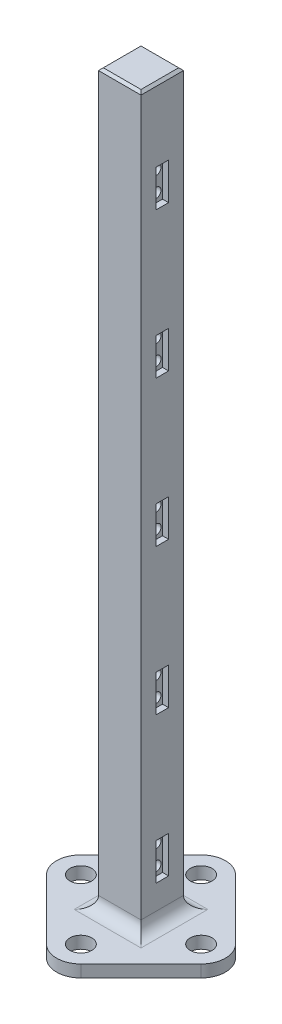
SolidWorks part; units mm, degrees
ref_plane "Front" through (0, 0, 0) normal (0, 0, 1) x (1, 0, 0)
ref_plane "Top" through (0, 0, 0) normal (0, 1, 0) x (1, 0, 0)
ref_plane "Right" through (0, 0, 0) normal (1, 0, 0) x (0, 0, -1)
ref_axis "Axis1" through (0, 55, 0) along (0, -1, 0)
ref_axis "Axis2" through (88.99, 0, 0) along (-1, 0, 0)
ref_axis "Axis3" through (0, 0, 55) along (0, 0, -1)
sketch "Sketch1" plane through (0, 0, 0) normal (0, 1, 0) x (1, 0, 0)
  line L0 (-24.75, 0) -> (0, 24.75) construction
  line L9 (-24.75, 0) -> (0, -24.75) construction
  line L11 (0, 24.75) -> (24.75, 0) construction
  line L12 (0, -24.75) -> (24.75, 0) construction
  line L13 (-24.75, 0) -> (24.75, 0) construction
  line L14 (0, 24.75) -> (0, -24.75) construction
  line L15 (-31.8211, 7.0711) -> (-7.0711, 31.8211)
  line L16 (7.0711, 31.8211) -> (31.8211, 7.0711)
  line L17 (7.0711, -31.8211) -> (31.8211, -7.0711)
  line L18 (-31.8211, -7.0711) -> (-7.0711, -31.8211)
  line L19 (0, -38.8921) -> (38.8921, 0) construction
  line L20 (-38.8921, 0) -> (0, -38.8921) construction
  line L21 (0, 38.8921) -> (38.8921, 0) construction
  line L22 (-38.8921, 0) -> (0, 38.8921) construction
  arc A4 (7.0711, -31.8211) -> (-7.0711, -31.8211) centre (0, -24.75) cw
  arc A5 (31.8211, 7.0711) -> (31.8211, -7.0711) centre (24.75, 0) cw
  arc A6 (-7.0711, 31.8211) -> (7.0711, 31.8211) centre (0, 24.75) cw
  arc A7 (-31.8211, 7.0711) -> (-31.8211, -7.0711) centre (-24.75, 0) ccw
  circle A8 centre (0, 24.75) radius 4.5
  circle A9 centre (24.75, 0) radius 4.5
  circle A10 centre (0, -24.75) radius 4.5
  circle A11 centre (-24.75, 0) radius 4.5
  point P1 (0, 0)
  dimension "D3" = 10
  dimension "D4" = 9
  dimension "D1" = 49.5
  dimension "D2" = 10
extrude "Boss-Extrude1" add sketch "Sketch1" along normal mid plane 5
sketch "Sketch2" plane through (0, 2.5, 0) normal (0, 1, 0) x (1, 0, 0)
  line L0 (-8.75, 8.75) -> (8.75, -8.75) construction
  line L1 (-8.75, 8.75) -> (8.75, 8.75)
  line L2 (-8.75, 8.75) -> (-8.75, -8.75)
  line L3 (-8.75, -8.75) -> (8.75, -8.75)
  line L4 (8.75, 8.75) -> (8.75, -8.75)
  line L5 (-7.0711, 31.8211) -> (-31.8211, 7.0711) construction
  dimension "D1" = 17.5
extrude "Boss-Extrude2" add sketch "Sketch2" along normal blind 300
sketch "Sketch3" plane through (8.75, 0, 0) normal (1, 0, 0) x (0, 0, -1)
  line L0 (7.0711, 2.5) -> (31.8211, 2.5) construction
  line L1 (-2.6, 17.5) -> (2.6, 17.5)
  line L2 (-2.6, 17.5) -> (-2.6, 32.7)
  line L3 (-2.6, 32.7) -> (2.6, 32.7)
  line L4 (2.6, 17.5) -> (2.6, 32.7)
  point P4 (0, 17.5)
  dimension "D1" = 5.2
  dimension "D2" = 15.2
  dimension "D3" = 15
extrude "Cut-Extrude1" cut sketch "Sketch3" against normal blind 2.5
hole_wizard "Ø4.0mm Dowel Hole1" positions "Sketch5" profile "Sketch6" hole size "Ø4.0" standard "DIN" end condition through all
sketch "Sketch5" plane through (6.25, 0, 0) normal (1, 0, 0) x (0, 0, -1)
  line L0 (0, 32.7) -> (0, 29.2) construction
  line L1 (2.6, 32.7) -> (-2.6, 32.7) construction
  line L2 (0, 29.2) -> (0, 21) construction
  line L3 (0, 21) -> (0, 17.5) construction
  line L4 (-2.6, 17.5) -> (2.6, 17.5) construction
  point P0 (0, 21)
  point P2 (0, 29.2)
  dimension "D1" = 3.5
sketch "Sketch6" plane through (6.25, 21, 0) normal (0, 1, 0) x (0, 0, -1)
  line L0 (0, 0) -> (0, 41)
  line L1 (0, 41) -> (2, 41)
  line L2 (2, 41) -> (2, 0)
  line L5 (2, 0) -> (0, 0)
  line L11 (0, -6.35) -> (0, 107.95) construction
  dimension "Thru Hole Dia." = 4
  dimension "Thru Hole Depth" = 41
pattern_linear "LPattern1" count 5 spacing 60 along (0, 1, 0) of "Ø4.0mm Dowel Hole1", "Cut-Extrude1"
chamfer "Chamfer1" distance 1 angle 45 4 edges at (0, 302.5, -8.75) (8.75, 302.5, 0) (0, 302.5, 8.75) (-8.75, 302.5, 0)
fillet "Fillet1" radius 5 4 edges at (0, 2.5, -8.75) (8.75, 2.5, 0) (0, 2.5, 8.75) (-8.75, 2.5, 0)
